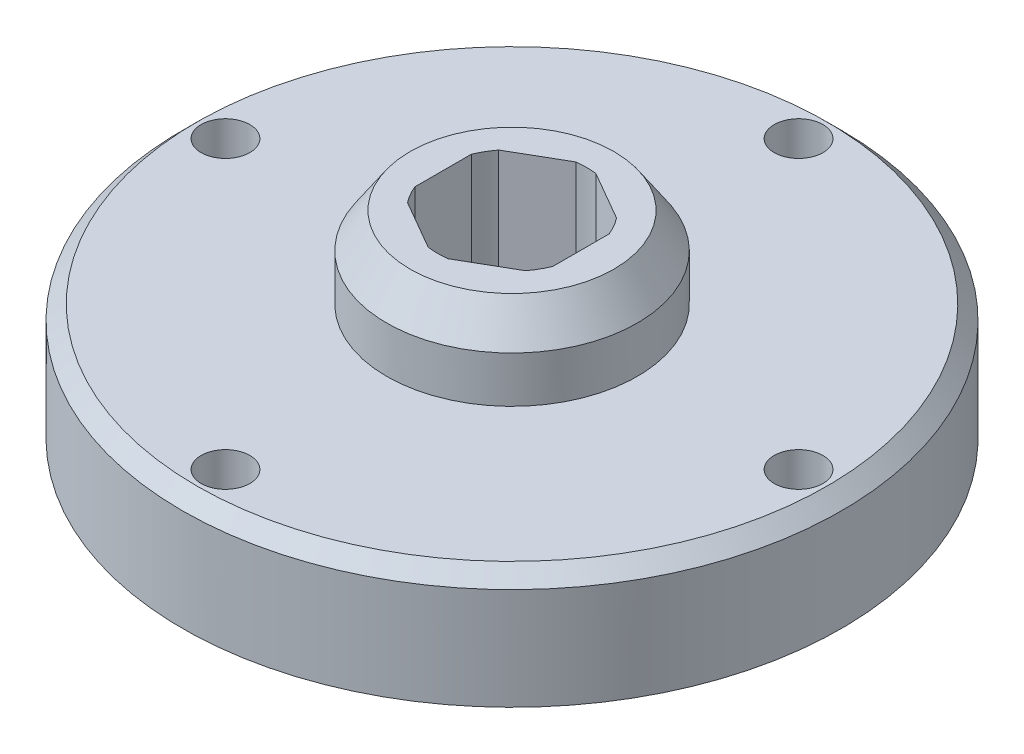
SolidWorks part; units mm, degrees
material "Nylon 6/10"
ref_plane "Front Plane" through (0, 0, 0) normal (0, 0, 1) x (1, 0, 0)
ref_plane "Top Plane" through (0, 0, 0) normal (0, 1, 0) x (1, 0, 0)
ref_plane "Right Plane" through (0, 0, 0) normal (1, 0, 0) x (0, 0, -1)
sketch "Sketch1" plane through (0, 0, 0) normal (0, 0, 1) x (1, 0, 0)
  line L0 (6.8, 0) -> (6.8, 4.953)
  line L1 (6.8, 4.953) -> (5.2, 4.953)
  line L2 (5.2, 4.953) -> (5.2, 13.7758)
  line L3 (5.2, 13.7758) -> (7.112, 13.7758)
  line L5 (8.9, 8.1133) -> (23, 8.1133)
  line L6 (23, 8.1133) -> (23, 0)
  line L7 (23, 0) -> (6.8, 0)
  line L8 (7.112, 13.7758) -> (8.9, 11.1133)
  line L9 (8.9, 11.1133) -> (8.9, 8.1133)
  line L10 (0, 0) -> (0, 16.4092) construction
  dimension "D1" = 6.8
  dimension "D2" = 23
  dimension "D3" = 4.953
  dimension "D4" = 8.9
  dimension "D5" = 5.6625
  dimension "D6" = 8.1133
  dimension "D7" = 3
  dimension "D8" = 7.112
  dimension "D9" = 5.2
revolve "Revolve1" add sketch "Sketch1" angle 360 about L10
sketch "Sketch2" plane through (0, 0, 0) normal (0, 1, 0) x (1, 0, 0)
  circle A0 centre (0, 0) radius 20 construction
  point P3 (-20, 0)
  dimension "D1" = 40
hole_wizard "M3 Clearance Hole1" positions "Sketch2" profile "Sketch3" hole size "M3" standard "ANSI Metric" end condition through all
sketch "Sketch3" plane through (-20, 0, 0) normal (1, 0, 0) x (0, 0, -1)
  line L0 (0, 0) -> (0, 13.7758)
  line L1 (0, 13.7758) -> (1.7, 13.7758)
  line L2 (1.7, 13.7758) -> (1.7, 0)
  line L5 (1.7, 0) -> (0, 0)
  line L11 (0, -6.35) -> (0, 107.95) construction
  dimension "Thru Hole Dia." = 3.4
  dimension "Thru Hole Depth" = 13.7758
pattern_circular "CirPattern1" count 4 over 360 about axis through (0, 0, 0) along (0, -1, 0) of "M3 Clearance Hole1"
sketch "Sketch4" plane through (0, 4.953, 0) normal (0, -1, 0) x (1, 0, 0)
  line L1 (4.8125, 2.7785) -> (0, 5.557)
  line L2 (0, 5.557) -> (-4.8125, 2.7785)
  line L3 (-4.8125, 2.7785) -> (-4.8125, -2.7785)
  line L4 (-4.8125, -2.7785) -> (0, -5.557)
  line L5 (0, -5.557) -> (4.8125, -2.7785)
  line L6 (4.8125, -2.7785) -> (4.8125, 2.7785)
  circle A0 centre (0, 0) radius 4.8125 construction
  circle A1 centre (0, 0) radius 5.2 construction
  circle A2 centre (0, 0) radius 5.2
  circle M9 centre (0, 0) radius 5.2
  dimension "D1" = 9.625
extrude "Boss-Extrude1" add sketch "Sketch4" against normal up to surface (8.8228 mm away) contours L2 M9 | L3 M9 | L4 M9 | L5 M9 | L6 M9 | L1 M9 region at (2.484, 4.953, 4.3024) region at (4.968, 4.953, 0) region at (-2.484, 4.953, 4.3024) region at (2.484, 4.953, -4.3024) region at (-4.968, 4.953, 0) region at (-2.484, 4.953, -4.3024) up to face at (0, 13.7758, -5.2)
chamfer "Chamfer1" distance 0.75 angle 45 1 edges at (0, 0, -6.8)
chamfer "Chamfer2" distance 1 angle 45 1 edges at (0, 8.1133, -23)
other "Move Face1" flip direction yes face at (0, 11.1133, -8.9) offset 0.15 parameters "D1"=0.15
